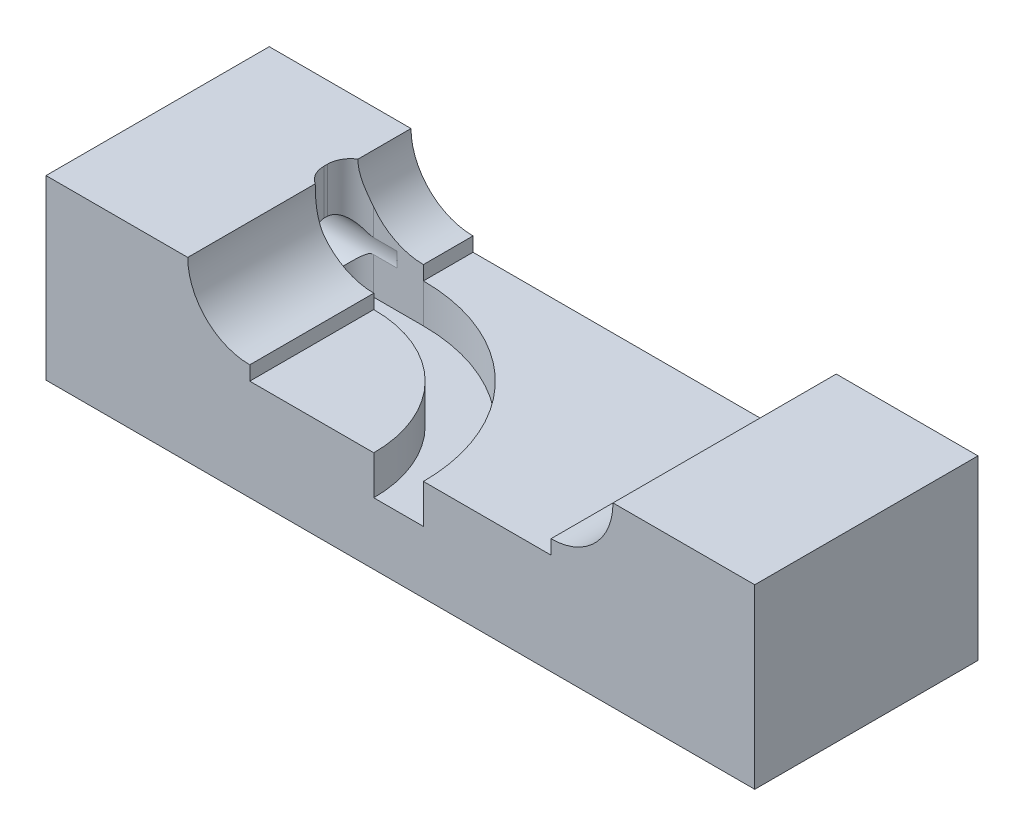
SolidWorks part; units mm, degrees
ref_plane "Front Plane" through (0, 0, 0) normal (0, 0, 1) x (1, 0, 0)
ref_plane "Top Plane" through (0, 0, 0) normal (0, 1, 0) x (1, 0, 0)
ref_plane "Right Plane" through (0, 0, 0) normal (1, 0, 0) x (0, 0, -1)
sketch "Sketch1" plane through (0, 0, 0) normal (0, 1, 0) x (1, 0, 0)
  line L1 (-12.7, -4.0005) -> (12.7, -4.0005)
  line L2 (-12.7, -4.0005) -> (-12.7, 4.0005)
  line L3 (-12.7, 4.0005) -> (12.7, 4.0005)
  line L4 (12.7, -4.0005) -> (12.7, 4.0005)
  line L5 (-12.7, -4.0005) -> (12.7, 4.0005) construction
  line L6 (-12.7, 4.0005) -> (12.7, -4.0005) construction
  point P0 (0, 0)
  dimension "D1" = 25.4
  dimension "D2" = 8.001
extrude "Boss-Extrude1" add sketch "Sketch1" along normal blind 6.35
sketch "Sketch2" plane through (0, 0, -4.0005) normal (0, 0, -1) x (-1, 0, 0)
  line L0 (5.3975, 6.35) -> (-5.3975, 6.35) construction
  line L1 (5.3975, 4.1275) -> (-5.3975, 4.1275)
  line L2 (5.3975, 8.5725) -> (-5.3975, 8.5725)
  line L3 (12.7, 6.35) -> (-12.7, 6.35) construction
  line L4 (-12.7, 0) -> (12.7, 0) construction
  line L6 (12.7, 6.35) -> (12.7, 0) construction
  line L7 (-12.7, 6.35) -> (-12.7, 0) construction
  arc A0 (5.3975, 4.1275) -> (5.3975, 8.5725) centre (5.3975, 6.35) ccw
  arc A1 (-5.3975, 8.5725) -> (-5.3975, 4.1275) centre (-5.3975, 6.35) ccw
  point P2 (0, 6.35)
  dimension "D1" = 6.35
  dimension "D2" = 10.795
  dimension "D3" = 4.445
extrude "Cut-Extrude1" cut sketch "Sketch2" against normal blind 25.4
ref_plane "Plane1" through (0, 4.1275, 0) normal (0, 1, 0) x (1, 0, 0)
sketch "Sketch4" plane through (0, 4.1275, 0) normal (0, 1, 0) x (1, 0, 0)
  line L1 (0.8255, -4.0005) -> (-0.9525, -4.0005)
  line L2 (-5.3975, 0.4445) -> (-7.1855, 0.4445)
  line L3 (-8.011, 1.27) -> (-8.011, 1.397)
  line L4 (-7.1855, 2.2225) -> (-5.3975, 2.2225)
  arc A0 (-0.9525, -4.0005) -> (-5.3975, 0.4445) centre (-5.3975, -4.0005) ccw
  arc A1 (0.8255, -4.0005) -> (-5.3975, 2.2225) centre (-5.3975, -4.0005) ccw
  arc A2 (-8.011, 1.27) -> (-7.1855, 0.4445) centre (-7.1855, 1.27) ccw
  arc A3 (-7.1855, 2.2225) -> (-8.011, 1.397) centre (-7.1855, 1.397) ccw
  dimension "D1" = 8.89
  dimension "D2" = 12.446
  dimension "D3" = 2.6135
  dimension "D4" = 1.778
  dimension "D5" = 0.8255
extrude "Cut-Extrude2" cut sketch "Sketch4" against normal blind 1.905 and the other way through all
ref_plane "Plane3" through (-12.7, 0, 0) normal (-1, 0, 0) x (0, 0, 1)
sketch "Sketch5" plane through (12.7, 0, 0) normal (1, 0, 0) x (0, 0, -1)
  line L0 (-4.0005, 6.35) -> (-4.0005, 0) construction
  line L1 (-4.0005, 6.35) -> (4.0005, 6.35) construction
  circle A0 centre (1.3335, 3.81) radius 0.9271
  dimension "D2" = 1.8542
  dimension "D1" = 5.334
  dimension "D3" = 2.54
extrude "Cut-Extrude3" cut sketch "Sketch5" along normal blind 6.35 from surface starting at plane "Plane3"
fillet "Fillet3" [suppressed] radius 6.35
sketch "Sketch6" plane through (0, 4.1275, 0) normal (0, 1, 0) x (1, 0, 0)
  line L1 (5.3975, -4.0005) -> (-5.3975, -4.0005)
  line L2 (5.3975, -4.0005) -> (5.3975, 4.0005)
  line L3 (5.3975, 4.0005) -> (-5.3975, 4.0005)
  line L4 (-5.3975, -4.0005) -> (-5.3975, 4.0005)
extrude "Cut-Extrude4" cut sketch "Sketch6" against normal blind 0.508
